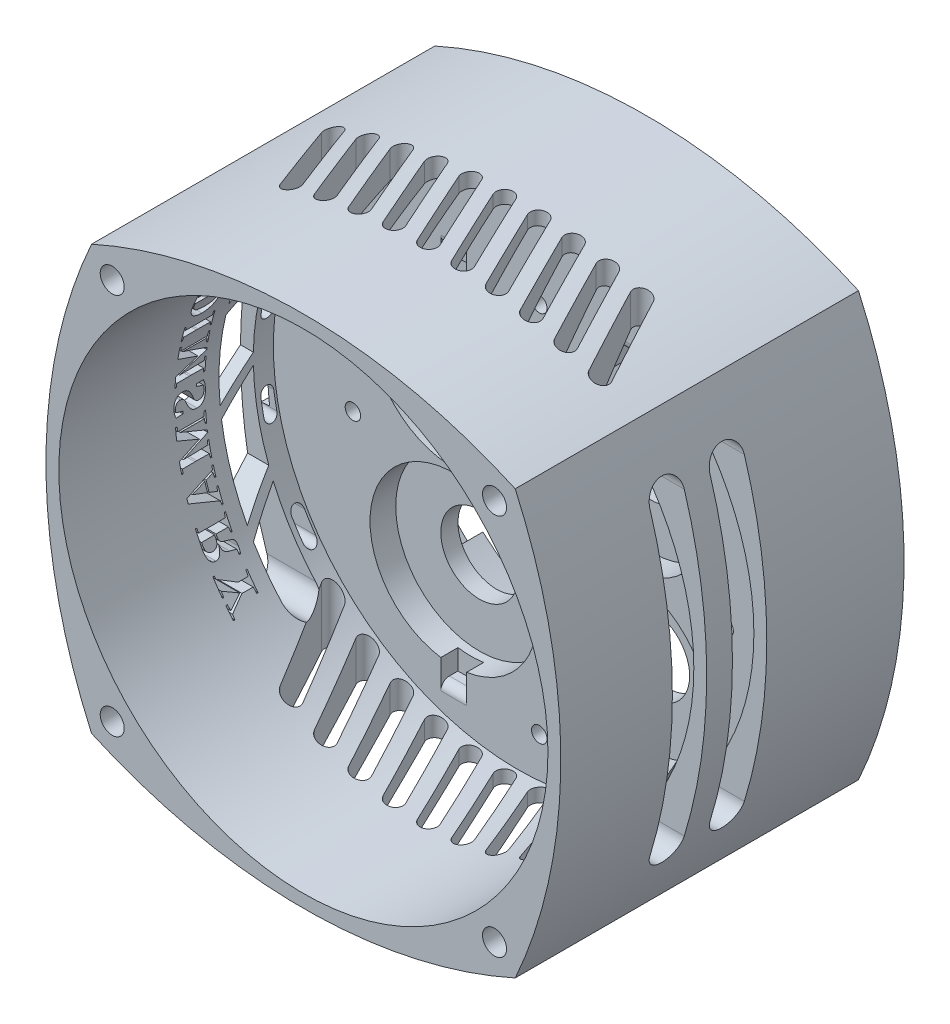
SolidWorks part; units mm, degrees
other "标注1"
sketch "草图13" plane through (-30, -30, 0) normal (-0.3557, -0.7189, -0.5972) x (0.1193, 0.5988, -0.792)
ref_plane "前视基准面" through (0, 0, 0) normal (0, 0, 1) x (1, 0, 0)
ref_plane "上视基准面" through (0, 0, 0) normal (0, 1, 0) x (1, 0, 0)
ref_plane "右视基准面" through (0, 0, 0) normal (1, 0, 0) x (0, 0, -1)
sketch "草图2" plane through (0, 0, 0) normal (0, 0, 1) x (1, 0, 0)
  line L0 (19.0096, -24.5333) -> (17.553, -22.4531)
  line L1 (15.0955, -24.1738) -> (16.5521, -26.2541)
  line L2 (16.5521, -26.2541) -> (19.0096, -24.5333)
  line L3 (-24.5333, -19.0096) -> (-22.4531, -17.553)
  line L4 (-24.1738, -15.0955) -> (-26.2541, -16.5521)
  line L5 (-26.2541, -16.5521) -> (-24.5333, -19.0096)
  line L6 (-19.0096, 24.5333) -> (-17.553, 22.4531)
  line L7 (-15.0955, 24.1738) -> (-16.5521, 26.2541)
  line L8 (-16.5521, 26.2541) -> (-19.0096, 24.5333)
  line L9 (24.5333, 19.0096) -> (22.4531, 17.553)
  line L10 (26.2541, 16.5521) -> (24.5333, 19.0096)
  line L11 (24.1738, 15.0955) -> (26.2541, 16.5521)
  line L12 (22.6863, 13.6961) -> (22.6863, -13.6961)
  line L13 (9.0863, 24.8936) -> (9.0863, -24.8936)
  line L14 (-22.6863, -13.6961) -> (-22.6863, 13.6961)
  line L15 (-16.6863, -20.5869) -> (-16.6863, 20.5869)
  circle A0 centre (0, 0) radius 26.5
  circle A1 centre (0, 0) radius 28.5
  arc A2 (24.6863, -24.6863) -> (24.6863, 24.6863) centre (-30, 0) ccw
  arc A3 (-24.6863, -24.6863) -> (24.6863, -24.6863) centre (0, 30) ccw
  arc A4 (24.6863, 24.6863) -> (-24.6863, 24.6863) centre (0, -30) ccw
  arc A5 (-24.6863, 24.6863) -> (-24.6863, -24.6863) centre (30, 0) ccw
sketch "草图3" plane through (0, 0, 0) normal (0, 0, 1) x (1, 0, 0)
  line L0 (0, 30) -> (0, 0) construction
  line L1 (-30, 30) -> (30, 30) construction
  line L2 (-30, 30) -> (-30, -30) construction
  line L3 (-30, -30) -> (30, -30) construction
  line L4 (30, 30) -> (30, -30) construction
  line L5 (-30, 0) -> (0, 0) construction
  arc A1 (24.6863, 24.6863) -> (-24.6863, 24.6863) centre (0, -30) ccw
  arc A4 (24.6863, -24.6863) -> (24.6863, 24.6863) centre (-30, 0) ccw
  arc A5 (-24.6863, -24.6863) -> (24.6863, -24.6863) centre (0, 30) ccw
  arc A6 (-24.6863, 24.6863) -> (-24.6863, -24.6863) centre (30, 0) ccw
  dimension "D1" = 60
extrude "凸台-拉伸1" add sketch "草图3" along normal blind 40
sketch "草图4" plane through (0, 0, 0) normal (0, 0, -1) x (-1, 0, 0)
  line L0 (-22.1663, 17.9626) -> (-22.1411, 17.9449)
  line L1 (-24.4606, 14.686) -> (-24.4354, 14.6683)
  line L2 (-17.9626, -22.1663) -> (-17.9449, -22.1411)
  line L3 (-14.686, -24.4606) -> (-14.6683, -24.4354)
  line L4 (22.1663, -17.9626) -> (22.1411, -17.9449)
  line L5 (24.4606, -14.686) -> (24.4354, -14.6683)
  line L6 (14.686, 24.4606) -> (14.6683, 24.4354)
  line L7 (17.9626, 22.1663) -> (17.9449, 22.1411)
  line L15 (-24.4606, 14.686) -> (-26.9504, 16.4294)
  line L16 (-26.9504, 16.4294) -> (-24.6561, 19.706)
  line L17 (-24.6561, 19.706) -> (-22.1663, 17.9626)
  line L18 (-24.4606, 14.686) -> (-26.9504, 16.4294)
  line L19 (-26.9504, 16.4294) -> (-24.6561, 19.706)
  line L20 (-24.6561, 19.706) -> (-22.1663, 17.9626)
  line L27 (-14.686, -24.4606) -> (-16.4294, -26.9504)
  line L28 (-16.4294, -26.9504) -> (-19.706, -24.6561)
  line L29 (-19.706, -24.6561) -> (-17.9626, -22.1663)
  line L30 (-14.686, -24.4606) -> (-16.4294, -26.9504)
  line L31 (-16.4294, -26.9504) -> (-19.706, -24.6561)
  line L32 (-19.706, -24.6561) -> (-17.9626, -22.1663)
  line L38 (24.6561, -19.706) -> (22.1663, -17.9626)
  line L39 (26.9504, -16.4294) -> (24.6561, -19.706)
  line L40 (24.4606, -14.686) -> (26.9504, -16.4294)
  line L41 (24.6561, -19.706) -> (22.1663, -17.9626)
  line L42 (26.9504, -16.4294) -> (24.6561, -19.706)
  line L43 (24.4606, -14.686) -> (26.9504, -16.4294)
  line L49 (14.686, 24.4606) -> (16.4294, 26.9504)
  line L50 (19.706, 24.6561) -> (17.9626, 22.1663)
  line L51 (16.4294, 26.9504) -> (19.706, 24.6561)
  line L52 (14.686, 24.4606) -> (16.4294, 26.9504)
  line L53 (19.706, 24.6561) -> (17.9626, 22.1663)
  line L54 (16.4294, 26.9504) -> (19.706, 24.6561)
  arc A0 (-22.1411, 17.9449) -> (-24.4354, 14.6683) centre (0, 0) ccw
  circle A1 centre (0, 0) radius 28.5 construction
  arc A2 (-17.9449, -22.1411) -> (-14.6683, -24.4354) centre (0, 0) ccw
  arc A3 (22.1411, -17.9449) -> (24.4354, -14.6683) centre (0, 0) ccw
  arc A4 (17.9449, 22.1411) -> (14.6683, 24.4354) centre (0, 0) ccw
  dimension "D1" = 0.5
  dimension "D2" = 0.5
  dimension "D3" = 0.5
  dimension "D4" = 0.5
sketch "草图5" plane through (0, 0, 0) normal (0, 0, -1) x (-1, 0, 0)
  circle A0 centre (0, 0) radius 28.8
extrude "切除-拉伸3" cut sketch "草图5" against normal blind 10
sketch "草图10" plane through (0, 0, 0) normal (0, 0, -1) x (-1, 0, 0)
  line L0 (0.4598, -0.4598) -> (35355.7989, -35355.7989) construction
  line L1 (-0.9416, -0.9416) -> (-35356.2807, -35356.2807) construction
  line L2 (-20.895, 23.3699) -> (-23.3699, 20.895)
  line L3 (-23.3699, 20.895) -> (-21.352, 18.8771)
  line L4 (20.895, -23.3699) -> (23.3699, -20.895)
  line L5 (23.3699, -20.895) -> (21.352, -18.8771)
  line L6 (20.895, 23.3699) -> (18.8771, 21.352)
  line L7 (-23.3699, -20.895) -> (-20.895, -23.3699)
  line L8 (-20.895, -23.3699) -> (-18.8771, -21.352)
  line L9 (23.3699, 20.895) -> (20.895, 23.3699)
  line L10 (-18.8771, 21.352) -> (-20.895, 23.3699)
  line L13 (21.352, 18.8771) -> (23.3699, 20.895)
  line L14 (18.8771, -21.352) -> (20.895, -23.3699)
  line L16 (-21.352, -18.8771) -> (-23.3699, -20.895)
  arc A0 (-18.8771, 21.352) -> (-21.352, 18.8771) centre (0, 0) ccw
  arc A1 (-21.352, -18.8771) -> (-18.8771, -21.352) centre (0, 0) ccw
  arc A2 (18.8771, -21.352) -> (21.352, -18.8771) centre (0, 0) ccw
  arc A3 (21.352, 18.8771) -> (18.8771, 21.352) centre (0, 0) ccw
  dimension "D1" = 3.5
  dimension "D2" = 1.75
  dimension "D3" = 31.3
  dimension "D4" = 31.3
  dimension "D5" = 3.5
  dimension "D6" = 1.75
  dimension "D7" = 31.3
  dimension "D8" = 31.3
extrude "切除-拉伸4" cut sketch "草图10" against normal blind 8
ref_plane "基准面5" through (0, 0, 0) normal (-0.7071, 0.7071, 0) x (0.7071, 0.7071, 0)
sketch "草图12" plane through (0, 0, 0) normal (-0.7071, 0.7071, 0) x (0.7071, 0.7071, 0)
  line L0 (0, -40) -> (0, 0) construction
  line L1 (31.3, -8) -> (0, -8)
  line L2 (31.3, -8) -> (31.3, -4.8)
  line L3 (31.3, -4.8) -> (0, -4.8)
  line L4 (0, -8) -> (0, -4.8)
  dimension "D1" = 3.2
revolve "切除-旋转4" cut sketch "草图12" angle 13 about L4
sketch "草图14" plane through (0, 0, 0) normal (-0.7071, 0.7071, 0) x (0.7071, 0.7071, 0)
  line L0 (0, -40) -> (0, 0) construction
  line L1 (-31.3, -8) -> (0, -8)
  line L2 (-31.3, -8) -> (-31.3, -4.8)
  line L3 (-31.3, -4.8) -> (0, -4.8)
  line L4 (0, -8) -> (0, -4.8)
  dimension "D1" = 3.2
revolve "切除-旋转5" cut sketch "草图14" angle 13 about L4
ref_plane "基准面6" through (0, 0, 0) normal (-0.7071, -0.7071, 0) x (0, 0, 1)
sketch "草图15" plane through (0, 0, 0) normal (-0.7071, -0.7071, 0) x (0, 0, 1)
  line L0 (40, 0) -> (0, 0) construction
  line L1 (8, -31.3) -> (4.8, -31.3)
  line L2 (8, -31.3) -> (8, 0)
  line L3 (8, 0) -> (4.8, 0)
  line L4 (4.8, -31.3) -> (4.8, 0)
  dimension "D1" = 3.2
revolve "切除-旋转6" cut sketch "草图15" angle 13 about L3
sketch "草图16" plane through (0, 0, 0) normal (-0.7071, -0.7071, 0) x (0, 0, 1)
  line L5 (40, 0) -> (0, 0) construction
  line L6 (8, 31.3) -> (4.8, 31.3)
  line L7 (8, 31.3) -> (8, 0)
  line L8 (8, 0) -> (4.8, 0)
  line L9 (4.8, 31.3) -> (4.8, 0)
  dimension "D1" = 3.2
revolve "切除-旋转9" cut sketch "草图16" angle 13 about L8
fillet "圆角1" radius 10 4 edges at (23.3353, 20.8604, 6.4) (-20.8604, 23.3353, 6.4) (-23.3353, -20.8604, 6.4) (20.8604, -23.3353, 6.4)
sketch "草图18" plane through (0, 0, 8) normal (0, 0, -1) x (-1, 0, 0)
  line L15 (14.9317, 24.2886) -> (16.503, 26.5326)
  line L16 (16.503, 26.5326) -> (19.2881, 24.5825)
  line L17 (19.2881, 24.5825) -> (17.7168, 22.3384)
  line L18 (14.9317, 24.2886) -> (16.503, 26.5326)
  line L19 (16.503, 26.5326) -> (19.2881, 24.5825)
  line L20 (19.2881, 24.5825) -> (17.7168, 22.3384)
  line L27 (-24.2886, 14.9317) -> (-26.5326, 16.503)
  line L28 (-26.5326, 16.503) -> (-24.5825, 19.2881)
  line L29 (-24.5825, 19.2881) -> (-22.3384, 17.7168)
  line L30 (-24.2886, 14.9317) -> (-26.5326, 16.503)
  line L31 (-26.5326, 16.503) -> (-24.5825, 19.2881)
  line L32 (-24.5825, 19.2881) -> (-22.3384, 17.7168)
  line L39 (-19.2881, -24.5825) -> (-17.7168, -22.3384)
  line L40 (-16.503, -26.5326) -> (-19.2881, -24.5825)
  line L41 (-14.9317, -24.2886) -> (-16.503, -26.5326)
  line L42 (-19.2881, -24.5825) -> (-17.7168, -22.3384)
  line L43 (-16.503, -26.5326) -> (-19.2881, -24.5825)
  line L44 (-14.9317, -24.2886) -> (-16.503, -26.5326)
  line L51 (24.2886, -14.9317) -> (26.5326, -16.503)
  line L52 (26.5326, -16.503) -> (24.5825, -19.2881)
  line L53 (24.5825, -19.2881) -> (22.3384, -17.7168)
  line L54 (24.2886, -14.9317) -> (26.5326, -16.503)
  line L55 (26.5326, -16.503) -> (24.5825, -19.2881)
  line L56 (24.5825, -19.2881) -> (22.3384, -17.7168)
  arc A1 (17.7168, 22.3384) -> (14.9317, 24.2886) centre (0, 0) ccw
  arc A2 (-22.3384, 17.7168) -> (-24.2886, 14.9317) centre (0, 0) ccw
  arc A3 (22.3384, -17.7168) -> (24.2886, -14.9317) centre (0, 0) ccw
  arc A4 (-17.7168, -22.3384) -> (-14.9317, -24.2886) centre (0, 0) ccw
  dimension "D1" = 0.2
  dimension "D2" = 0.2
  dimension "D3" = 0.2
  dimension "D4" = 0.2
extrude "切除-拉伸5" cut sketch "草图18" along normal blind 4
sketch "草图20" plane through (0, 0, 0) normal (0, 0, 1) x (1, 0, 0)
  line L0 (-19.0096, 24.5333) -> (-17.553, 22.4531)
  line L1 (-16.5521, 26.2541) -> (-19.0096, 24.5333)
  line L2 (-15.0955, 24.1738) -> (-16.5521, 26.2541)
  line L3 (-24.5333, -19.0096) -> (-22.4531, -17.553)
  line L4 (-24.1738, -15.0955) -> (-26.2541, -16.5521)
  line L5 (-26.2541, -16.5521) -> (-24.5333, -19.0096)
  line L6 (16.5521, -26.2541) -> (19.0096, -24.5333)
  line L7 (15.0955, -24.1738) -> (16.5521, -26.2541)
  line L8 (19.0096, -24.5333) -> (17.553, -22.4531)
  line L9 (26.2541, 16.5521) -> (24.5333, 19.0096)
  line L10 (24.1738, 15.0955) -> (26.2541, 16.5521)
  line L11 (24.5333, 19.0096) -> (22.4531, 17.553)
  line L12 (-22.6863, -13.6961) -> (-22.6863, 13.6961)
  line L13 (-11.6863, -23.7841) -> (-11.6863, 23.7841)
  line L14 (22.6863, 13.6961) -> (22.6863, -13.6961)
  line L15 (16.6863, 20.5869) -> (16.6863, -20.5869)
  line L16 (7.5533, -12.6646) -> (8.5631, -12.6646)
  line L17 (11.496, -15.909) -> (11.496, -16.936)
  line L18 (8.7583, -10.6646) -> (7.7073, -10.6646)
  line L19 (11.496, -7.1455) -> (11.496, -8.1725)
  line L20 (-6.5171, -16.946) -> (-6.5171, -15.9216)
  line L21 (-3.5348, -12.6646) -> (-2.5249, -12.6646)
  line L22 (13.496, -8.1631) -> (13.496, -7.1381)
  line L23 (13.496, -16.9434) -> (13.496, -15.9184)
  line L24 (-6.5171, 3.054) -> (-6.5171, 4.0784)
  line L25 (-3.5744, 7.122) -> (-2.5564, 7.122)
  line L26 (7.5848, 7.122) -> (8.6028, 7.122)
  line L27 (11.496, 4.091) -> (11.496, 3.064)
  line L28 (8.6869, 9.122) -> (7.6512, 9.122)
  line L29 (11.496, 12.8545) -> (11.496, 11.8275)
  line L30 (-6.5171, -8.1598) -> (-6.5171, -7.1355)
  line L31 (-2.6789, -10.6646) -> (-3.73, -10.6646)
  line L32 (-8.5171, -15.9055) -> (-8.5171, -16.9332)
  line L33 (-8.5171, -7.1482) -> (-8.5171, -8.1759)
  line L34 (-2.6229, 9.122) -> (-3.6585, 9.122)
  line L35 (-6.5171, 11.8402) -> (-6.5171, 12.8645)
  line L36 (-8.5171, 4.0945) -> (-8.5171, 3.0668)
  line L37 (-8.5171, 12.8518) -> (-8.5171, 11.8241)
  line L38 (13.496, 11.8369) -> (13.496, 12.8619)
  line L39 (13.496, 3.0566) -> (13.496, 4.0816)
  circle A0 centre (0, 0) radius 26.5
  circle A1 centre (0, 0) radius 28.5
  arc A2 (-24.6863, 24.6863) -> (-24.6863, -24.6863) centre (30, 0) ccw
  arc A3 (24.6863, -24.6863) -> (24.6863, 24.6863) centre (-30, 0) ccw
  arc A4 (24.6863, 24.6863) -> (-24.6863, 24.6863) centre (0, -30) ccw
  arc A5 (-24.6863, -24.6863) -> (24.6863, -24.6863) centre (0, 30) ccw
  arc A6 (7.5533, -12.6646) -> (11.496, -16.936) centre (12.5142, -12.0407) ccw
  arc A7 (8.5631, -12.6646) -> (11.496, -15.909) centre (12.5142, -12.0407) ccw
  arc A8 (11.496, -8.1725) -> (8.7583, -10.6646) centre (12.5142, -12.0407) ccw
  arc A9 (11.496, -7.1455) -> (7.7073, -10.6646) centre (12.5142, -12.0407) ccw
  arc A10 (-6.5171, -16.946) -> (-2.5249, -12.6646) centre (-7.4858, -12.0407) ccw
  arc A11 (-6.5171, -15.9216) -> (-3.5348, -12.6646) centre (-7.4858, -12.0407) ccw
  arc A12 (13.496, -15.9184) -> (13.496, -8.1631) centre (12.5142, -12.0407) ccw
  arc A13 (15.1576, -7.7966) -> (16.6863, -6.9478) centre (15.6863, -6.9478) ccw
  arc A14 (16.6863, -17.1336) -> (15.1576, -16.2848) centre (15.6863, -17.1336) ccw
  arc A15 (13.496, -16.9434) -> (15.1576, -16.2848) centre (12.5142, -12.0407) ccw
  arc A16 (15.1576, -7.7966) -> (13.496, -7.1381) centre (12.5142, -12.0407) ccw
  arc A17 (-6.5171, 3.054) -> (-2.5564, 7.122) centre (-7.4858, 7.9593) ccw
  arc A18 (-6.5171, 4.0784) -> (-3.5744, 7.122) centre (-7.4858, 7.9593) ccw
  arc A19 (7.5848, 7.122) -> (11.496, 3.064) centre (12.5142, 7.9593) ccw
  arc A20 (8.6028, 7.122) -> (11.496, 4.091) centre (12.5142, 7.9593) ccw
  arc A21 (11.496, 11.8275) -> (8.6869, 9.122) centre (12.5142, 7.9593) ccw
  arc A22 (11.496, 12.8545) -> (7.6512, 9.122) centre (12.5142, 7.9593) ccw
  arc A23 (-3.73, -10.6646) -> (-6.5171, -8.1598) centre (-7.4858, -12.0407) ccw
  arc A24 (-2.6789, -10.6646) -> (-6.5171, -7.1355) centre (-7.4858, -12.0407) ccw
  arc A25 (-8.5171, -8.1759) -> (-8.5171, -15.9055) centre (-7.4858, -12.0407) ccw
  arc A26 (-10.1529, -16.27) -> (-8.5171, -16.9332) centre (-7.4858, -12.0407) ccw
  arc A27 (-10.1529, -16.27) -> (-11.6863, -17.1159) centre (-10.6863, -17.1159) ccw
  arc A28 (-11.6863, -6.9656) -> (-10.1529, -7.8114) centre (-10.6863, -6.9656) ccw
  arc A29 (-8.5171, -7.1482) -> (-10.1529, -7.8114) centre (-7.4858, -12.0407) ccw
  arc A30 (-2.6229, 9.122) -> (-6.5171, 12.8645) centre (-7.4858, 7.9593) ccw
  arc A31 (-3.6585, 9.122) -> (-6.5171, 11.8402) centre (-7.4858, 7.9593) ccw
  arc A32 (-10.1529, 3.73) -> (-11.6863, 2.8841) centre (-10.6863, 2.8841) ccw
  arc A33 (-11.6863, 13.0344) -> (-10.1529, 12.1886) centre (-10.6863, 13.0344) ccw
  arc A34 (-10.1529, 3.73) -> (-8.5171, 3.0668) centre (-7.4858, 7.9593) ccw
  arc A35 (-8.5171, 12.8518) -> (-10.1529, 12.1886) centre (-7.4858, 7.9593) ccw
  arc A36 (-8.5171, 11.8241) -> (-8.5171, 4.0945) centre (-7.4858, 7.9593) ccw
  arc A37 (13.496, 3.0566) -> (15.1576, 3.7152) centre (12.5142, 7.9593) ccw
  arc A38 (15.1576, 12.2034) -> (13.496, 12.8619) centre (12.5142, 7.9593) ccw
  arc A39 (15.1576, 12.2034) -> (16.6863, 13.0522) centre (15.6863, 13.0522) ccw
  arc A40 (13.496, 4.0816) -> (13.496, 11.8369) centre (12.5142, 7.9593) ccw
  arc A41 (16.6863, 2.8664) -> (15.1576, 3.7152) centre (15.6863, 2.8664) ccw
sketch "草图22" plane through (0, 0, 40) normal (0, 0, 1) x (1, 0, 0)
  circle A0 centre (12.5142, -12.0407) radius 4.5
  circle A1 centre (-7.4858, -12.0407) radius 4.5
  circle A2 centre (12.5142, 7.9593) radius 4.5
  circle A3 centre (-7.4858, 7.9593) radius 4.5
  dimension "D1" = 9
extrude "切除-拉伸6" cut sketch "草图22" against normal blind 57
sketch "草图23" plane through (0, 0, 40) normal (0, 0, 1) x (1, 0, 0)
  circle A1 centre (12.5142, -12.0407) radius 9.75
  circle A8 centre (-7.4858, -12.0407) radius 9.75
  circle A9 centre (12.5142, 7.9593) radius 9.75
  circle A10 centre (-7.4858, 7.9593) radius 9.75
  dimension "D1" = 19.5
extrude "切除-拉伸7" cut sketch "草图23" against normal offset from surface (28 mm away) 2 up to face at (-11.9858, -12.0407, 10)
sketch "草图26" plane through (0, 0, 40) normal (0, 0, 1) x (1, 0, 0)
  circle A0 centre (0, 0) radius 28.5
extrude "切除-拉伸9" cut sketch "草图26" against normal offset from surface (25 mm away) 3 up to face at (-17.2358, -12.0407, 12)
sketch "草图27" plane through (0, 0, 40) normal (0, 0, 1) x (1, 0, 0)
  line L0 (0, 0) -> (-35355.3391, 35355.3391) construction
  line L1 (0, 0) -> (35355.3391, 35355.3391) construction
  line L2 (22.2739, -22.2739) -> (22.2739, 22.2739) construction
  line L3 (22.2739, 22.2739) -> (-22.2739, 22.2739) construction
  line L4 (-22.2739, 22.2739) -> (-22.2739, -22.2739) construction
  line L5 (-22.2739, -22.2739) -> (22.2739, -22.2739) construction
  circle A0 centre (22.2739, 22.2739) radius 1.4
  circle A1 centre (22.2739, -22.2739) radius 1.4
  circle A2 centre (-22.2739, -22.2739) radius 1.4
  circle A3 centre (-22.2739, 22.2739) radius 1.4
  circle A4 centre (0, 0) radius 28.5 construction
  dimension "D1" = 2.8
  dimension "D2" = 31.5
extrude "切除-拉伸10" cut sketch "草图27" against normal blind 7
sketch "草图28" plane through (0, 0, 15) normal (0, 0, 1) x (1, 0, 0)
  line L0 (2.4943, -3.7475) -> (2.4943, 49996.2525) construction
  line L1 (4.8197, -1.9718) -> (-49995.1803, -1.9718) construction
  line L2 (2.4943, -23.6929) -> (24.2154, -1.9718) construction
  line L3 (24.2154, -1.9718) -> (2.4943, 19.7493) construction
  line L4 (2.4943, 19.7493) -> (-19.2268, -1.9718) construction
  line L5 (-19.2268, -1.9718) -> (2.4943, -23.6929) construction
  circle A0 centre (24.2154, -1.9718) radius 0.9
  circle A1 centre (2.4943, -23.6929) radius 0.9
  circle A2 centre (2.4943, 19.7493) radius 0.9
  circle A3 centre (-19.2268, -1.9718) radius 0.9
  dimension "D1" = 1.8
extrude "切除-拉伸11" cut sketch "草图28" against normal blind 3
sketch "草图29" plane through (0, 0, 15) normal (0, 0, 1) x (1, 0, 0)
  line L0 (12.5142, 7.9593) -> (12.5142, 16.13) construction
  line L1 (14.0526, 16.13) -> (11.0526, 16.13)
  line L2 (14.0526, 16.13) -> (14.0526, 19.9593)
  line L3 (14.0526, 19.9593) -> (11.0526, 19.9593)
  line L4 (11.0526, 16.13) -> (11.0526, 19.9593)
  line L5 (-7.4858, -21.1676) -> (-7.4858, -12.0407) construction
  line L6 (14.0526, -24.0407) -> (11.0526, -24.0407)
  line L7 (14.0526, -24.0407) -> (14.0526, -20.8226)
  line L8 (14.0526, -20.8226) -> (11.0526, -20.8226)
  line L9 (11.0526, -24.0407) -> (11.0526, -20.8226)
  line L10 (-5.9858, -24.0407) -> (-8.9858, -24.0407)
  line L11 (-5.9858, -24.0407) -> (-5.9858, -21.1676)
  line L12 (-5.9858, -21.1676) -> (-8.9858, -21.1676)
  line L13 (-8.9858, -24.0407) -> (-8.9858, -21.1676)
  line L14 (-5.9858, 14.5321) -> (-8.9858, 14.5321)
  line L15 (-5.9858, 14.5321) -> (-5.9858, 19.9593)
  line L16 (-5.9858, 19.9593) -> (-8.9858, 19.9593)
  line L17 (-8.9858, 14.5321) -> (-8.9858, 19.9593)
  line L18 (-7.4858, 14.5321) -> (-7.4858, 7.9593) construction
  circle A0 centre (12.5142, -12.0407) radius 9.75 construction
  circle A1 centre (12.5142, 7.9593) radius 9.75 construction
  circle A2 centre (-7.4858, 7.9593) radius 9.75 construction
  circle A3 centre (-7.4858, -12.0407) radius 9.75 construction
  dimension "D1" = 3
  dimension "D2" = 3
  dimension "D3" = 3
  dimension "D4" = 3
  dimension "D5" = 12
  dimension "D6" = 12
  dimension "D7" = 12
  dimension "D8" = 12
extrude "切除-拉伸12" cut sketch "草图29" against normal blind 2
fillet "圆角2" radius 1 4 edges at (-7.4858, 19.9593, 15) (12.5526, 19.9593, 15) (-7.4858, -24.0407, 15) (12.5526, -24.0407, 15)
sketch "草图30" plane through (0, 0, 0) normal (0, 1, 0) x (1, 0, 0)
  line L0 (16.7738, -16) -> (21, -25.0631)
  line L2 (19.1874, -25.9083) -> (14.9612, -16.8452)
  line L4 (24.6863, -40) -> (24.6863, 0) construction
  line L5 (2.7642, -15) -> (22.2642, -15) construction
  line L6 (30, -40) -> (30, 0) construction
  line L7 (12.7738, -16) -> (17, -25.0631)
  line L8 (15.1874, -25.9083) -> (10.9612, -16.8452)
  line L9 (8.7738, -16) -> (13, -25.0631)
  line L10 (11.1874, -25.9083) -> (6.9612, -16.8452)
  line L11 (4.7738, -16) -> (9, -25.0631)
  line L12 (7.1874, -25.9083) -> (2.9612, -16.8452)
  line L13 (0.7738, -16) -> (5, -25.0631)
  line L14 (3.1874, -25.9083) -> (-1.0388, -16.8452)
  line L15 (-3.2262, -16) -> (1, -25.0631)
  line L16 (-0.8126, -25.9083) -> (-5.0388, -16.8452)
  line L17 (-7.2262, -16) -> (-3, -25.0631)
  line L18 (-4.8126, -25.9083) -> (-9.0388, -16.8452)
  line L19 (-11.2262, -16) -> (-7, -25.0631)
  line L20 (-8.8126, -25.9083) -> (-13.0388, -16.8452)
  line L21 (-15.2262, -16) -> (-11, -25.0631)
  line L22 (-12.8126, -25.9083) -> (-17.0388, -16.8452)
  line L23 (-19.2262, -16) -> (-15, -25.0631)
  line L24 (-16.8126, -25.9083) -> (-21.0388, -16.8452)
  arc A0 (16.7738, -16) -> (14.9612, -16.8452) centre (15.8675, -16.4226) ccw
  arc A1 (19.1874, -25.9083) -> (21, -25.0631) centre (20.0937, -25.4857) ccw
  arc A2 (12.7738, -16) -> (10.9612, -16.8452) centre (11.8675, -16.4226) ccw
  arc A3 (15.1874, -25.9083) -> (17, -25.0631) centre (16.0937, -25.4857) ccw
  arc A4 (8.7738, -16) -> (6.9612, -16.8452) centre (7.8675, -16.4226) ccw
  arc A5 (11.1874, -25.9083) -> (13, -25.0631) centre (12.0937, -25.4857) ccw
  arc A6 (4.7738, -16) -> (2.9612, -16.8452) centre (3.8675, -16.4226) ccw
  arc A7 (7.1874, -25.9083) -> (9, -25.0631) centre (8.0937, -25.4857) ccw
  arc A8 (0.7738, -16) -> (-1.0388, -16.8452) centre (-0.1325, -16.4226) ccw
  arc A9 (3.1874, -25.9083) -> (5, -25.0631) centre (4.0937, -25.4857) ccw
  arc A10 (-3.2262, -16) -> (-5.0388, -16.8452) centre (-4.1325, -16.4226) ccw
  arc A11 (-0.8126, -25.9083) -> (1, -25.0631) centre (0.0937, -25.4857) ccw
  arc A12 (-7.2262, -16) -> (-9.0388, -16.8452) centre (-8.1325, -16.4226) ccw
  arc A13 (-4.8126, -25.9083) -> (-3, -25.0631) centre (-3.9063, -25.4857) ccw
  arc A14 (-11.2262, -16) -> (-13.0388, -16.8452) centre (-12.1325, -16.4226) ccw
  arc A15 (-8.8126, -25.9083) -> (-7, -25.0631) centre (-7.9063, -25.4857) ccw
  arc A16 (-15.2262, -16) -> (-17.0388, -16.8452) centre (-16.1325, -16.4226) ccw
  arc A17 (-12.8126, -25.9083) -> (-11, -25.0631) centre (-11.9063, -25.4857) ccw
  arc A18 (-19.2262, -16) -> (-21.0388, -16.8452) centre (-20.1325, -16.4226) ccw
  arc A19 (-16.8126, -25.9083) -> (-15, -25.0631) centre (-15.9063, -25.4857) ccw
  dimension "D1" = 10
  dimension "D2" = 2
  dimension "D3" = 25
  dimension "D4" = 1
  dimension "D5" = 9
  dimension "D6" = 10
extrude "切除-拉伸13" cut sketch "草图30" against normal mid plane 79
sketch "草图31" plane through (0, 0, 0) normal (1, 0, 0) x (0, 0, -1)
  line L0 (-25, -17.5) -> (-25, 17.5) construction
  line L1 (-27, -17.5) -> (-27, 17.5)
  line L2 (-23, -17.5) -> (-23, 17.5)
  line L3 (-27, 0) -> (-40, 0) construction
  line L4 (-40, 24.6863) -> (-40, -24.6863) construction
  line L5 (-18, -17.5) -> (-18, 17.5) construction
  line L6 (-20, -17.5) -> (-20, 17.5)
  line L7 (-16, -17.5) -> (-16, 17.5)
  arc A0 (-27, -17.5) -> (-23, -17.5) centre (-25, -17.5) ccw
  arc A1 (-23, 17.5) -> (-27, 17.5) centre (-25, 17.5) ccw
  arc A2 (-20, -17.5) -> (-16, -17.5) centre (-18, -17.5) ccw
  arc A3 (-16, 17.5) -> (-20, 17.5) centre (-18, 17.5) ccw
  point P2 (-25, 0)
  point P15 (-18, 0)
  dimension "D1" = 2
  dimension "D2" = 35
  dimension "D3" = 13
  dimension "D4" = 2
extrude "切除-拉伸14" cut sketch "草图31" along normal blind 79
sketch "草图32" plane through (0, 0, 0) normal (1, 0, 0) x (0, 0, -1)
  line L0 (-23, 17.5) -> (-23, -17.5) construction
  line L1 (-23, 17.5) -> (-23, -17.5) construction
  line L2 (-19.334, 19.0239) -> (-19.334, 24.6863) construction
  line L28 (-16, 15.4345) -> (-16, 5.161) construction
  line L34 (-21.334, 6.7051) -> (-21.334, -2.7796)
  line L36 (-17.334, 10.031) -> (-17.334, 0.5464)
  line L53 (-21.334, 19.0218) -> (-21.334, 8.0056)
  line L55 (-17.334, 19.0261) -> (-17.334, 11.3316)
  line L56 (-40, 24.6863) -> (0, 24.6863) construction
  line L57 (-19.334, -18.9739) -> (-19.334, -24.6362) construction
  line L58 (-21.334, 8.0056) -> (-17.334, 11.3316)
  line L59 (-21.334, 6.7051) -> (-17.334, 10.031)
  line L60 (-21.334, -2.7796) -> (-17.334, 0.5464)
  line L61 (-21.334, -4.0801) -> (-17.334, -0.7541)
  line L62 (-21.334, -13.2902) -> (-17.334, -9.9642)
  line L63 (-21.334, -14.5907) -> (-17.334, -11.2647)
  line L64 (-21.334, -4.0801) -> (-21.334, -13.2902)
  line L65 (-17.334, -0.7541) -> (-17.334, -9.9642)
  line L66 (-21.334, -14.5907) -> (-21.334, -18.9739)
  line L67 (-17.334, -11.2647) -> (-17.334, -18.9739)
  line L68 (-16, 16.4345) -> (-16, 14.4345) construction
  line L69 (-16, 17.5) -> (-16, -17.5) construction
  line L70 (-15.25, 16.4345) -> (-15.25, 14.4345)
  line L71 (-16.75, 16.4345) -> (-16.75, 14.4345)
  line L72 (-16, 6.161) -> (-16, 4.161) construction
  line L73 (-15.25, 6.161) -> (-15.25, 4.161)
  line L74 (-16.75, 6.161) -> (-16.75, 4.161)
  line L75 (-16, -4.1126) -> (-16, -6.1126) construction
  line L76 (-15.25, -4.1126) -> (-15.25, -6.1126)
  line L77 (-16.75, -4.1126) -> (-16.75, -6.1126)
  line L78 (-16, -14.3861) -> (-16, -16.3861) construction
  line L79 (-15.25, -14.3861) -> (-15.25, -16.3861)
  line L80 (-16.75, -14.3861) -> (-16.75, -16.3861)
  line L81 (-16, 5.161) -> (-16, -5.1126) construction
  line L82 (-16, -5.1126) -> (-16, -15.3861) construction
  arc A0 (-24.6597, -19.4708) -> (-23, -17.5) centre (-25, -17.5) ccw construction
  arc A19 (-17.334, 19.0261) -> (-21.334, 19.0218) centre (-19.334, 19.0239) ccw
  arc A20 (-21.334, -18.9739) -> (-17.334, -18.9739) centre (-19.334, -18.9739) ccw
  arc A21 (-15.25, 16.4345) -> (-16.75, 16.4345) centre (-16, 16.4345) ccw
  arc A22 (-16.75, 14.4345) -> (-15.25, 14.4345) centre (-16, 14.4345) ccw
  arc A23 (-15.25, 6.161) -> (-16.75, 6.161) centre (-16, 6.161) ccw
  arc A24 (-16.75, 4.161) -> (-15.25, 4.161) centre (-16, 4.161) ccw
  arc A25 (-15.25, -4.1126) -> (-16.75, -4.1126) centre (-16, -4.1126) ccw
  arc A26 (-16.75, -6.1126) -> (-15.25, -6.1126) centre (-16, -6.1126) ccw
  arc A27 (-15.25, -14.3861) -> (-16.75, -14.3861) centre (-16, -14.3861) ccw
  arc A28 (-16.75, -16.3861) -> (-15.25, -16.3861) centre (-16, -16.3861) ccw
  ellipse E0 centre (11.3935, 0) end of major axis (-49.7249, 0) minor radius 28.5 (-25.0631, -22.8747) -> (-16, -25.477) ccw construction
  text T0 "@DIMSMARY" font "思源宋体 Heavy" height 3.5
  point P38 (-16, 15.4345)
  point P49 (-16, 5.161)
  point P58 (-16, -5.1126)
  point P65 (-16, -15.3861)
  dimension "D5" = 1
  dimension "D1" = 4
  dimension "D2" = 38
  dimension "D3" = 1
  dimension "D4" = 1
  dimension "D6" = 1.5
  dimension "D7" = 2
extrude "切除-拉伸15" cut sketch "草图32" against normal blind 57
sketch "草图33" plane through (0, 0, 0) normal (0, 0, -1) x (-1, 0, 0)
  line L0 (27.7053, 16.4345) -> (26.7436, 16.1606)
  line L1 (28.2378, 14.4345) -> (27.2672, 14.1939)
  line L2 (29.6829, 6.161) -> (28.6881, 6.0583)
  line L3 (29.8555, 4.161) -> (28.858, 4.0916)
  line L4 (29.8589, -4.1126) -> (28.8612, -4.0441)
  line L5 (29.6878, -6.1126) -> (28.693, -6.0107)
  line L6 (28.2498, -14.3861) -> (27.279, -14.1464)
  line L7 (27.7191, -16.3861) -> (26.7571, -16.113)
  arc A1 (27.2672, 14.1939) -> (26.7436, 16.1606) centre (-30, 0) ccw
  arc A2 (28.2378, 14.4345) -> (27.7053, 16.4345) centre (-30, 0) ccw
  arc A3 (28.2378, 14.4345) -> (27.7053, 16.4345) centre (-30, 0) ccw
  arc A4 (23.7748, -24.2748) -> (23.7748, 24.2748) centre (-30, 0) ccw
  arc A5 (29.8555, 4.161) -> (29.6829, 6.161) centre (-30, 0) ccw
  arc A6 (29.8555, 4.161) -> (29.6829, 6.161) centre (-30, 0) ccw
  arc A7 (26.7571, -16.113) -> (27.279, -14.1464) centre (-30, 0) ccw
  arc A8 (28.858, 4.0916) -> (28.6881, 6.0583) centre (-30, 0) ccw
  arc A9 (29.6878, -6.1126) -> (29.8589, -4.1126) centre (-30, 0) ccw
  arc A10 (29.6878, -6.1126) -> (29.8589, -4.1126) centre (-30, 0) ccw
  arc A12 (27.7191, -16.3861) -> (28.2498, -14.3861) centre (-30, 0) ccw
  arc A13 (27.7191, -16.3861) -> (28.2498, -14.3861) centre (-30, 0) ccw
  arc A14 (28.693, -6.0107) -> (28.8612, -4.0441) centre (-30, 0) ccw
  dimension "D1" = 0
  dimension "D2" = 0
  dimension "D3" = 0
  dimension "D4" = 0
  dimension "D5" = 1
extrude "切除-拉伸16" cut sketch "草图33" against normal blind 16
